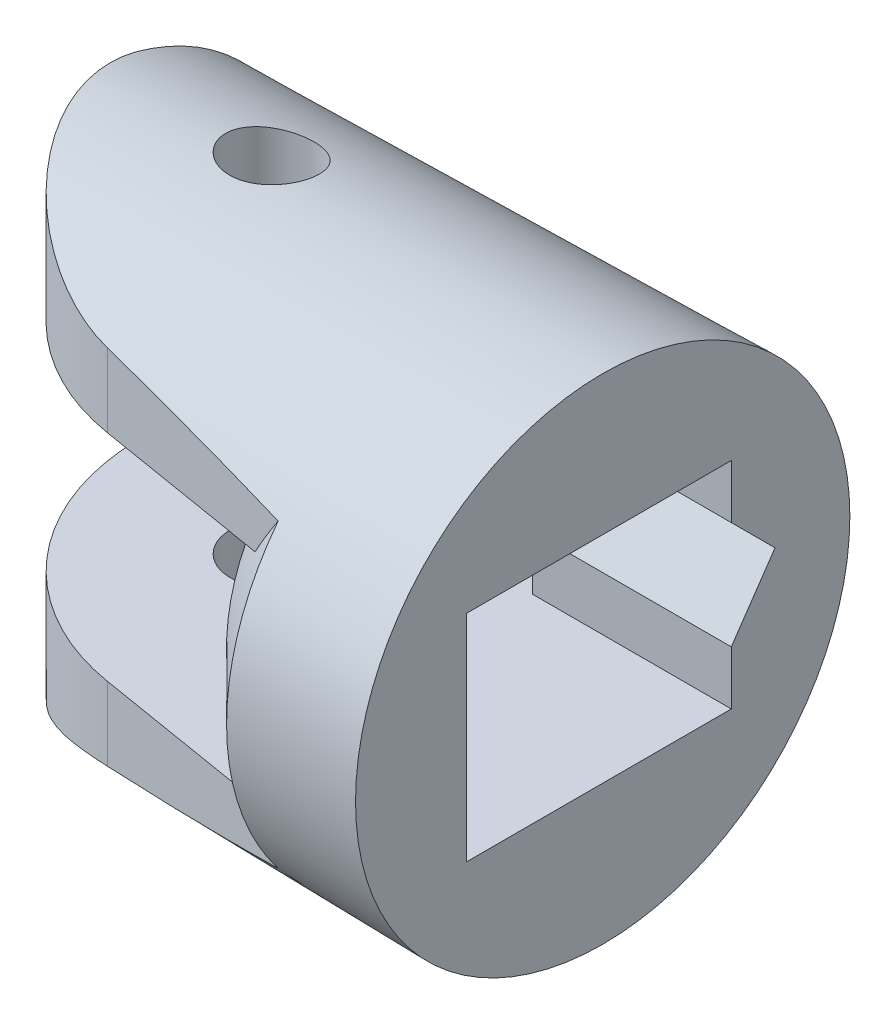
SolidWorks part; units mm, degrees
ref_plane "Front plane" through (0, 0, 0) normal (0, 0, 1) x (1, 0, 0)
ref_plane "Base plane" through (0, 0, 0) normal (0, 1, 0) x (1, 0, 0)
ref_plane "Right plane" through (0, 0, 0) normal (1, 0, 0) x (0, 0, -1)
sketch "Sketch1" plane through (0, 0, 0) normal (1, 0, 0) x (0, 0, -1)
  circle A0 centre (0, 0) radius 7.5
  dimension "D1" = 15
extrude "Boss-Extrude1" add sketch "Sketch1" along normal blind 18
sketch "Sketch2" plane through (0, 0, 0) normal (0, 1, 0) x (1, 0, 0)
  line L0 (10, 5.5026) -> (0, 5.4873)
  line L1 (18, -7.5) -> (18, 7.5) construction
  line L2 (10, -5.5) -> (5.8546, -4.8143)
  line L3 (0, 5.4873) -> (0, 2.2976)
  line L5 (0, 7.5) -> (0, -7.5) construction
  line L6 (10, -5.5) -> (10, -11.2528)
  line L9 (10, -11.2528) -> (-2.5986, -11.2528)
  line L10 (-2.5986, -11.2528) -> (-2.5986, 9.735)
  line L11 (-2.5986, 9.735) -> (10, 9.735)
  line L12 (10, 9.735) -> (10, 5.5026)
  arc A0 (0, 2.2976) -> (5.8546, -4.8143) centre (6.997, 2.0919) ccw
  dimension "D2" = 7
  dimension "D1" = 8
  dimension "D3" = 11.0026
  dimension "D4" = 8
  dimension "D5" = 2
extrude "Cut-Extrude1" cut sketch "Sketch2" against normal blind 18 and the other way blind 18 contours L11 L12 L0 L3 A0 L2 L6 L9 L10
sketch "Sketch3" plane through (0, 0, 0) normal (0, 1, 0) x (1, 0, 0)
  line L0 (10, 5.5026) -> (-1.0009, 5.5026)
  line L1 (10, -5.5) -> (-1.0009, -5.5)
  line L2 (-1.0009, -5.5) -> (-1.0009, 5.5026)
  line L3 (10, 5.5026) -> (10, -5.5)
extrude "Cut-Extrude2" cut sketch "Sketch3" against normal blind 3.25 and the other way blind 3.25
sketch "Sketch4" plane through (0, 0, 0) normal (0, 1, 0) x (1, 0, 0)
  line L0 (18, 7.5) -> (18, 1) construction
  line L1 (18, -7.5) -> (18, 7.5) construction
  line L2 (18, 1) -> (5, 1) construction
  circle A0 centre (5, 1) radius 1.25
  dimension "D3" = 2.5
  dimension "D2" = 13
  dimension "D1" = 6.5
extrude "Cut-Extrude3" cut sketch "Sketch4" against normal through all and the other way through all
sketch "Sketch5" plane through (18, 0, 0) normal (1, 0, 0) x (0, 0, -1)
  circle A0 centre (0, 0) radius 7.5 construction
  circle A1 centre (0, 0) radius 7.5
extrude "Cut-Extrude-Thin1" cut sketch "Sketch5" against normal blind 23.25 draft 1 thin draft outward yes thin type one direction wall 10
fillet "Fillet1" radius 0.5 2 edges at (0, -3.9448, -5.4873) (0, 3.9448, -5.4873)
sketch "Sketch7" plane through (0, 0, 0) normal (0, 1, 0) x (1, 0, 0)
  line L1 (18, 7.5) -> (16, 7.5)
  line L2 (18, 7.5) -> (18, -7.6621)
  line L3 (18, -7.6621) -> (16, -7.6621)
  line L4 (16, 7.5) -> (16, -7.6621)
  dimension "D1" = 2
extrude "Cut-Extrude4" cut sketch "Sketch7" against normal blind 23.25 and the other way blind 23.25
chamfer "Chamfer1" distance 2 angle 45 1 edges at (10, 0, 7.3604) first distance on face at (10, 0, -0.001)
chamfer "Chamfer2" distance 1 angle 45 1 edges at (10, 0, -7.3604) first distance on face at (10, 0, -2.3742)
sketch "Sketch8" plane through (16, 0, 0) normal (1, 0, 0) x (0, 0, -1)
  line L0 (0, 0) -> (-4.1162, 0) construction
  line L1 (-4.1162, 0) -> (3.8838, 0) construction
  line L2 (3.8838, 0) -> (3.8838, 3.25) construction
  line L3 (3.8838, 3.25) -> (-4.1162, 3.25) construction
  line L4 (-4.1162, 3.25) -> (-4.1162, -3.25) construction
  line L5 (-4.1162, -3.25) -> (3.8838, -3.25) construction
  line L6 (3.8838, -3.25) -> (3.8838, 0) construction
  line L7 (3.8838, 1.625) -> (5.2049, 0.3038)
  line L8 (5.2049, 0.3038) -> (3.8838, -1.625)
  line L9 (3.8838, -1.625) -> (3.8838, -3.25)
  line L10 (3.8838, -3.25) -> (-4.1162, -3.25)
  line L11 (-4.1162, -3.25) -> (-4.1162, 3.25)
  line L12 (-4.1162, 3.25) -> (3.8838, 3.25)
  line L13 (3.8838, 3.25) -> (3.8838, 1.625)
  dimension "D1" = 6.5
  dimension "D2" = 3.25
  dimension "D3" = 8
  dimension "D4" = 1.625
  dimension "D5" = 100.591
  dimension "D6" = 1.625
extrude "Cut-Extrude5" cut sketch "Sketch8" against normal blind 10
